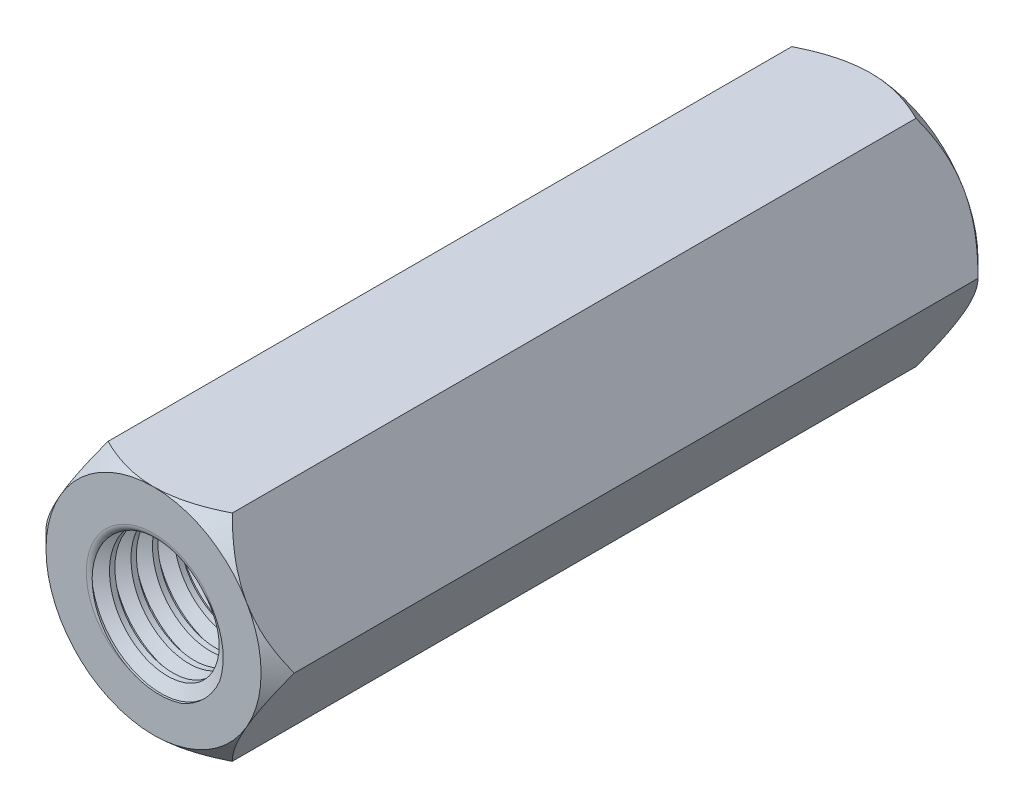
SolidWorks part; units mm, degrees
ref_plane "Front Plane" through (0, 0, 0) normal (0, 0, 1) x (1, 0, 0)
ref_plane "Top Plane" through (0, 0, 0) normal (0, 1, 0) x (1, 0, 0)
ref_plane "Right Plane" through (0, 0, 0) normal (1, 0, 0) x (0, 0, -1)
sketch "Sketch1" plane through (0, 0, 0) normal (0, 0, 1) x (1, 0, 0)
  line L1 (8.6603, 0) -> (4.3301, 7.5)
  line L2 (4.3301, 7.5) -> (-4.3301, 7.5)
  line L3 (-4.3301, 7.5) -> (-8.6603, 0)
  line L4 (-8.6603, 0) -> (-4.3301, -7.5)
  line L5 (-4.3301, -7.5) -> (4.3301, -7.5)
  line L6 (4.3301, -7.5) -> (8.6603, 0)
  circle A0 centre (0, 0) radius 7.5 construction
  dimension "D1" = 15
extrude "Boss-Extrude1" add sketch "Sketch1" along normal mid plane 50
sketch "Sketch3" plane through (0, 0, 25) normal (0, 0, 1) x (1, 0, 0)
  circle A0 centre (0, 0) radius 7.5
extrude "Cut-Extrude1" cut sketch "Sketch3" against normal through all draft 45 flip side to cut
mirror "Mirror1" about plane through (0, 0, 0) normal (0, 0, 1) of "Cut-Extrude1"
sketch "Sketch4" plane through (0, 0, 25) normal (0, 0, 1) x (1, 0, 0)
  circle A0 centre (0, 0) radius 4.19
  dimension "D1" = 8.38
extrude "Cut-Extrude2" cut sketch "Sketch4" against normal through all contours A0
fillet "Fillet2" radius 0.5 2 edges at (4.19, 0, -25) (4.19, 0, 25)
thread "Thread1" pitch 1.5 profile "Thread Profile1" start angle 0, offset 2, length 0, pitch 1.5, diameter 8.38
ref_plane "Plane1" through (-4.19, 0, 26.5) normal (0, -1, 0) x (-1, 0, 0)
sketch "Thread Profile1" plane through (-4.19, 0, 26.5) normal (0, -1, 0) x (-1, 0, 0)
  line L0 (0, 0) -> (0, 1.5) construction
  line L1 (0, 0) -> (0.8119, 0.4687)
  line L2 (0.8119, 0.4687) -> (0.8119, 0.6562)
  line L3 (0.8119, 0.6562) -> (0, 1.125)
  line L4 (0.8119, 0.5625) -> (0, 0.5625) construction
  line L11 (0, 0) -> (0, 1.125)
  point P2 (0, 0)
  dimension "Pitch" = 1.5
  dimension "Profile_Angle" = 60
  dimension "Profile_Land" = 0.1875
  dimension "Profile_Height" = 0.8119
